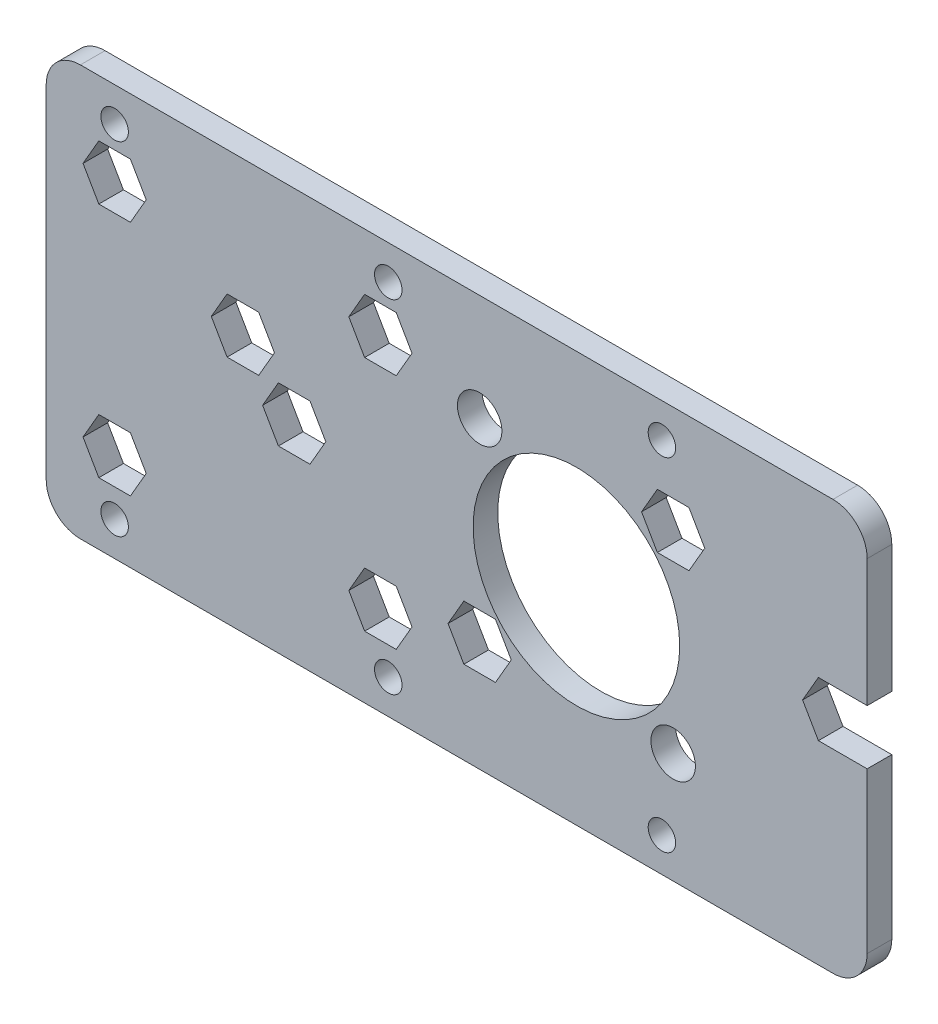
SolidWorks part; units mm, degrees
ref_plane "Front Plane" through (0, 0, 0) normal (0, 0, 1) x (1, 0, 0)
ref_plane "Top Plane" through (0, 0, 0) normal (0, 1, 0) x (1, 0, 0)
ref_plane "Right Plane" through (0, 0, 0) normal (1, 0, 0) x (0, 0, -1)
sketch "Sketch1" plane through (0, 0, 0) normal (0, 0, 1) x (1, 0, 0)
  line L1 (-31.2284, 4.7954) -> (-31.2284, 68.2954)
  line L2 (121.1716, 68.2954) -> (121.1716, 4.7954)
  line L6 (-24.8784, 74.6454) -> (114.8216, 74.6454)
  line L7 (-24.8784, -1.5546) -> (114.8216, -1.5546)
  line L9 (117.9829, 44.6616) -> (121.1716, 44.6616)
  line L10 (-12.6625, 59.0583) -> (-15.5954, 64.1383)
  line L11 (-15.5954, 64.1383) -> (-21.4613, 64.1383)
  line L12 (-21.4613, 64.1383) -> (-24.3942, 59.0583)
  line L13 (-24.3942, 59.0583) -> (-21.4613, 53.9783)
  line L14 (-21.4613, 53.9783) -> (-15.5954, 53.9783)
  line L15 (-15.5954, 53.9783) -> (-12.6625, 59.0583)
  line L16 (36.6774, 59.0583) -> (33.7444, 64.1383)
  line L17 (33.7444, 64.1383) -> (27.8785, 64.1383)
  line L18 (27.8785, 64.1383) -> (24.9456, 59.0583)
  line L19 (24.9456, 59.0583) -> (27.8785, 53.9783)
  line L20 (27.8785, 53.9783) -> (33.7444, 53.9783)
  line L21 (33.7444, 53.9783) -> (36.6774, 59.0583)
  line L22 (-12.6625, 15.0646) -> (-15.5954, 20.1446)
  line L23 (-15.5954, 20.1446) -> (-21.4613, 20.1446)
  line L24 (-21.4613, 20.1446) -> (-24.3942, 15.0646)
  line L25 (-24.3942, 15.0646) -> (-21.4613, 9.9846)
  line L26 (-21.4613, 9.9846) -> (-15.5954, 9.9846)
  line L27 (-15.5954, 9.9846) -> (-12.6625, 15.0646)
  line L28 (36.6774, 15.0646) -> (33.7444, 20.1446)
  line L29 (33.7444, 20.1446) -> (27.8785, 20.1446)
  line L30 (27.8785, 20.1446) -> (24.9456, 15.0646)
  line L31 (24.9456, 15.0646) -> (27.8785, 9.9846)
  line L32 (27.8785, 9.9846) -> (33.7444, 9.9846)
  line L33 (33.7444, 9.9846) -> (36.6774, 15.0646)
  line L34 (55.102, 18.9641) -> (52.1691, 24.0441)
  line L35 (52.1691, 24.0441) -> (46.3032, 24.0441)
  line L36 (46.3032, 24.0441) -> (43.3702, 18.9641)
  line L37 (43.3702, 18.9641) -> (46.3032, 13.8841)
  line L38 (46.3032, 13.8841) -> (52.1691, 13.8841)
  line L39 (52.1691, 13.8841) -> (55.102, 18.9641)
  line L40 (91.023, 54.8851) -> (88.0901, 59.9651)
  line L41 (88.0901, 59.9651) -> (82.2242, 59.9651)
  line L42 (82.2242, 59.9651) -> (79.2913, 54.8851)
  line L43 (79.2913, 54.8851) -> (82.2242, 49.8051)
  line L44 (82.2242, 49.8051) -> (88.0901, 49.8051)
  line L45 (88.0901, 49.8051) -> (91.023, 54.8851)
  line L46 (11.15, 46.3583) -> (8.2171, 51.4383)
  line L47 (8.2171, 51.4383) -> (2.3512, 51.4383)
  line L48 (2.3512, 51.4383) -> (-0.5817, 46.3583)
  line L49 (-0.5817, 46.3583) -> (2.3512, 41.2783)
  line L50 (2.3512, 41.2783) -> (8.2171, 41.2783)
  line L51 (8.2171, 41.2783) -> (11.15, 46.3583)
  line L52 (20.675, 36.8333) -> (17.7421, 41.9133)
  line L53 (17.7421, 41.9133) -> (11.8762, 41.9133)
  line L54 (11.8762, 41.9133) -> (8.9433, 36.8333)
  line L55 (8.9433, 36.8333) -> (11.8762, 31.7533)
  line L56 (11.8762, 31.7533) -> (17.7421, 31.7533)
  line L57 (17.7421, 31.7533) -> (20.675, 36.8333)
  line L58 (120.9159, 39.5816) -> (117.9829, 44.6616)
  line L59 (117.9829, 44.6616) -> (112.117, 44.6616)
  line L60 (112.117, 44.6616) -> (109.1841, 39.5816)
  line L61 (109.1841, 39.5816) -> (112.117, 34.5016)
  line L62 (112.117, 34.5016) -> (117.9829, 34.5016)
  line L63 (117.9829, 34.5016) -> (120.9159, 39.5816)
  line L64 (117.9829, 34.5016) -> (121.1716, 34.5016)
  circle A0 centre (83.0716, 4.7954) radius 2.5527
  circle A1 centre (83.0716, 68.2954) radius 2.5527
  circle A2 centre (-18.5284, 59.0583) radius 5.08 construction
  arc A3 (-31.2284, 68.2954) -> (-24.8784, 74.6454) centre (-24.8784, 68.2954) cw
  arc A4 (-31.2284, 4.7954) -> (-24.8784, -1.5546) centre (-24.8784, 4.7954) ccw
  arc A5 (114.8216, -1.5546) -> (121.1716, 4.7954) centre (114.8216, 4.7954) ccw
  arc A6 (114.8216, 74.6454) -> (121.1716, 68.2954) centre (114.8216, 68.2954) cw
  circle A9 centre (-18.5284, 59.0583) radius 2.5527
  circle A13 centre (32.2716, 68.2954) radius 2.5527
  circle A14 centre (30.8115, 59.0583) radius 2.5527
  circle A15 centre (5.2841, 46.3583) radius 2.5527
  circle A16 centre (14.8091, 36.8333) radius 2.5527
  circle A18 centre (-18.5284, 15.0646) radius 2.5527
  circle A23 centre (30.8115, 15.0646) radius 2.5527
  circle A24 centre (32.2716, 4.7954) radius 2.5527
  circle A25 centre (49.2361, 18.9641) radius 2.5527
  circle A26 centre (49.2361, 54.8851) radius 4.1275
  circle A27 centre (85.1571, 54.8851) radius 2.5527
  circle A28 centre (115.2331, 39.5816) radius 2.5527
  circle A29 centre (85.1571, 18.9641) radius 4.1275
  circle A30 centre (67.1966, 36.8333) radius 19.177
  circle A31 centre (30.8115, 59.0583) radius 5.08 construction
  circle A32 centre (-18.5284, 15.0646) radius 5.08 construction
  circle A33 centre (30.8115, 15.0646) radius 5.08 construction
  circle A34 centre (49.2361, 18.9641) radius 5.08 construction
  circle A35 centre (85.1571, 54.8851) radius 5.08 construction
  circle A36 centre (5.2841, 46.3583) radius 5.08 construction
  circle A37 centre (14.8091, 36.8333) radius 5.08 construction
  circle A38 centre (115.05, 39.5816) radius 5.08 construction
  circle A39 centre (-18.5284, 68.2954) radius 2.5527
  circle A40 centre (-18.5284, 4.7954) radius 2.5527
  point P114 (0, 0)
  point P115 (0, 0)
  point P116 (0, 0)
  point P117 (0, 0)
  point P118 (0, 0)
  point P119 (0, 0)
  point P120 (0, 0)
  point P121 (9.9996, 55.5051)
  point P122 (0, 0)
  dimension "D3" = 6.35
  dimension "D4" = 5.1054
  dimension "D6" = 50.8
  dimension "D12" = 50.8
  dimension "D14" = 16.0023
  dimension "D1" = 152.4
  dimension "D2" = 76.2
  dimension "D5" = 12.7
  dimension "D7" = 35.921
  dimension "D8" = 35.921
  dimension "D9" = 17.9605
  dimension "D10" = 18.0518
  dimension "D11" = 10.16
  dimension "D13" = 50.8
  dimension "D15" = 22.225
  dimension "D16" = 9.525
  dimension "D17" = 9.525
  dimension "D18" = 18.4246
  dimension "D19" = 4.1732
  dimension "D20" = 9.2371
  dimension "D21" = 43.9937
extrude "Boss-Extrude1" add sketch "Sketch1" along normal blind 4.572 contours A6 L6 A3 L1 A4 L7 A5 L2 A30 A29 A28 A26 A24 A39 A13 A1 A0 L57 L56 L55 L54 L53 L52 L51 L50 L49 L48 L47 L46 L45 L44 L43 L42 L41 L40 L39 region at (43.0593, 36.3477, 0)
